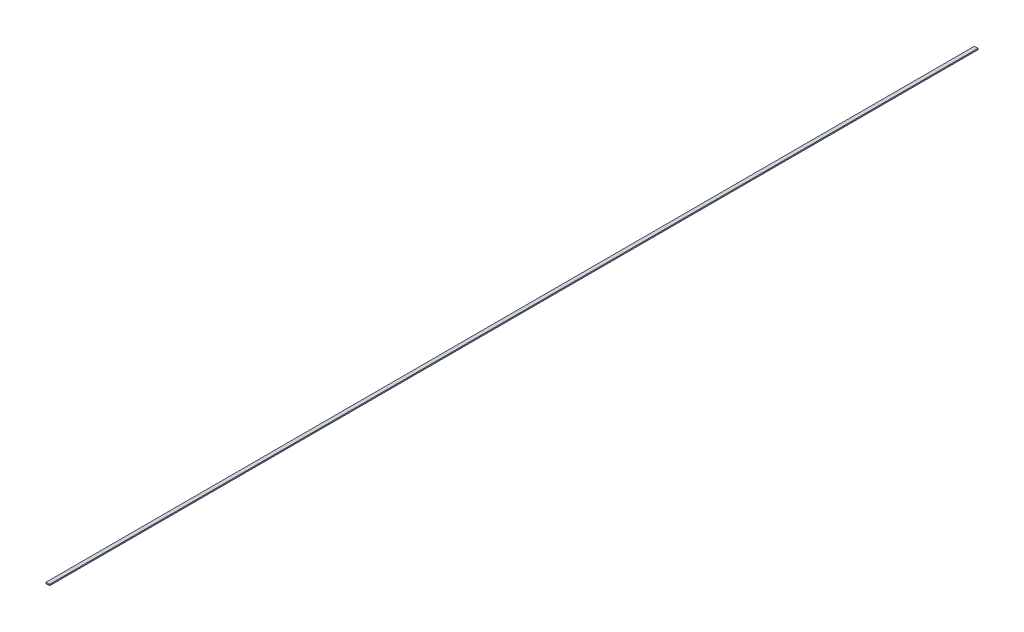
SolidWorks part; units mm, degrees
material "Thornel Mat VMA"
ref_plane "前视基准面" through (0, 0, 0) normal (0, 0, 1) x (1, 0, 0)
ref_plane "上视基准面" through (0, 0, 0) normal (0, 1, 0) x (1, 0, 0)
ref_plane "右视基准面" through (0, 0, 0) normal (1, 0, 0) x (0, 0, -1)
other "Configuration Table"
sketch "草图1" plane through (0, 0, 0) normal (0, 0, 1) x (1, 0, 0)
  line L1 (151.8745, -5.1918) -> (148.8745, -5.1918)
  line L2 (151.8745, -5.1918) -> (151.8745, -6.1918)
  line L3 (151.8745, -6.1918) -> (148.8745, -6.1918)
  line L4 (148.8745, -5.1918) -> (148.8745, -6.1918)
extrude "凸台-拉伸1" add sketch "草图1" along normal blind 762
